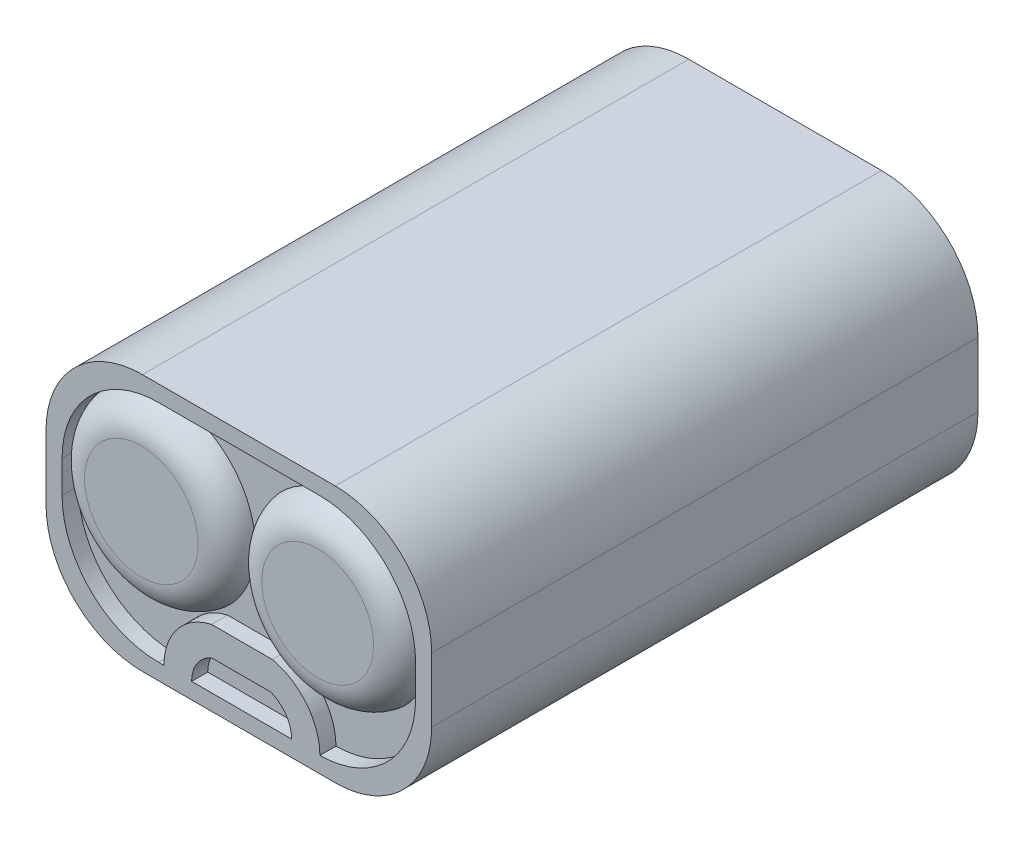
SolidWorks part; units mm, degrees
ref_plane "Front Plane" through (0, 0, 0) normal (0, 0, 1) x (1, 0, 0)
ref_plane "Top Plane" through (0, 0, 0) normal (0, 1, 0) x (1, 0, 0)
ref_plane "Right Plane" through (0, 0, 0) normal (1, 0, 0) x (0, 0, -1)
sketch "Sketch1" plane through (0, 0, 0) normal (0, 1, 0) x (1, 0, 0)
  line L1 (15.24, -21.59) -> (-15.24, -21.59)
  line L2 (15.24, -21.59) -> (15.24, 21.59)
  line L3 (15.24, 21.59) -> (-15.24, 21.59)
  line L4 (-15.24, -21.59) -> (-15.24, 21.59)
  line L5 (15.24, -21.59) -> (-15.24, 21.59) construction
  line L6 (15.24, 21.59) -> (-15.24, -21.59) construction
  point P0 (0, 0)
  dimension "D1" = 43.18
  dimension "D2" = 30.48
extrude "Boss-Extrude1" add sketch "Sketch1" along normal blind 20.32
sketch "Sketch2" plane through (0, 0, 21.59) normal (0, 0, 1) x (1, 0, 0)
  line L0 (-15.24, 0) -> (15.24, 0) construction
  line L1 (6.35, 1.27) -> (-6.35, 1.27)
  line L2 (13.97, 8.89) -> (13.97, 11.43)
  line L3 (6.35, 19.05) -> (-6.35, 19.05)
  line L4 (-13.97, 8.89) -> (-13.97, 11.43)
  line L5 (13.97, 1.27) -> (-13.97, 19.05) construction
  line L6 (13.97, 19.05) -> (-13.97, 1.27) construction
  line L7 (15.24, 20.32) -> (15.24, 0) construction
  line L8 (-1.1198, 1.27) -> (1.6086, 1.27) construction
  line L9 (-2.1566, 3.6652) -> (2.525, 3.6652)
  line L11 (-1.1198, 1.27) -> (1.6086, 1.27) construction
  line L12 (-2.1566, 5.9558) -> (2.6454, 5.9558)
  arc A0 (-6.35, 1.27) -> (-13.97, 8.89) centre (-6.35, 8.89) cw
  arc A1 (6.35, 1.27) -> (13.97, 8.89) centre (6.35, 8.89) ccw
  arc A2 (13.97, 11.43) -> (6.35, 19.05) centre (6.35, 11.43) ccw
  arc A3 (-6.35, 19.05) -> (-13.97, 11.43) centre (-6.35, 11.43) ccw
  arc A4 (-2.1566, 3.6652) -> (-3.7297, 1.27) centre (-1.1198, 1.27) ccw
  arc A5 (4.1731, 1.27) -> (2.525, 3.6652) centre (1.6086, 1.27) ccw
  arc A6 (-2.1566, 5.9558) -> (-5.9189, 1.27) centre (-1.1198, 1.27) ccw
  arc A7 (6.4077, 1.27) -> (2.6454, 5.9558) centre (1.6086, 1.27) ccw
  point P0 (0, 10.16)
  point P9 (0.2444, 1.27)
  point P30 (0.2444, 1.27)
  dimension "D5" = 7.62
  dimension "D1" = 17.78
  dimension "D2" = 27.94
  dimension "D3" = 10.16
  dimension "D4" = 15.24
fillet "Fillet1" radius 7.62 4 edges at (15.24, 0, 0) (-15.24, 0, 0) (15.24, 20.32, 0) (-15.24, 20.32, 0)
extrude "Cut-Extrude2" cut sketch "Sketch2" against normal blind 1.27 contours L1 A5 L9 A4 | A7 L1 A1 L2 A2 L3 A3 L4 A0 A6 L12 region at (0.2163, 2.3861, 21.59) region at (-0.03, 10.9914, 21.59)
sketch "Sketch3" plane through (0, 0, 20.32) normal (0, 0, 1) x (1, 0, 0)
  circle A2 centre (-6.9392, 11.6736) radius 6.9799
  circle A3 centre (6.9974, 11.6736) radius 6.9042
extrude "Boss-Extrude2" add sketch "Sketch3" along normal blind 2.032
fillet "Fillet2" radius 2.54 2 edges at (13.9016, 11.6736, 22.352) (0.0408, 11.6736, 22.352)
